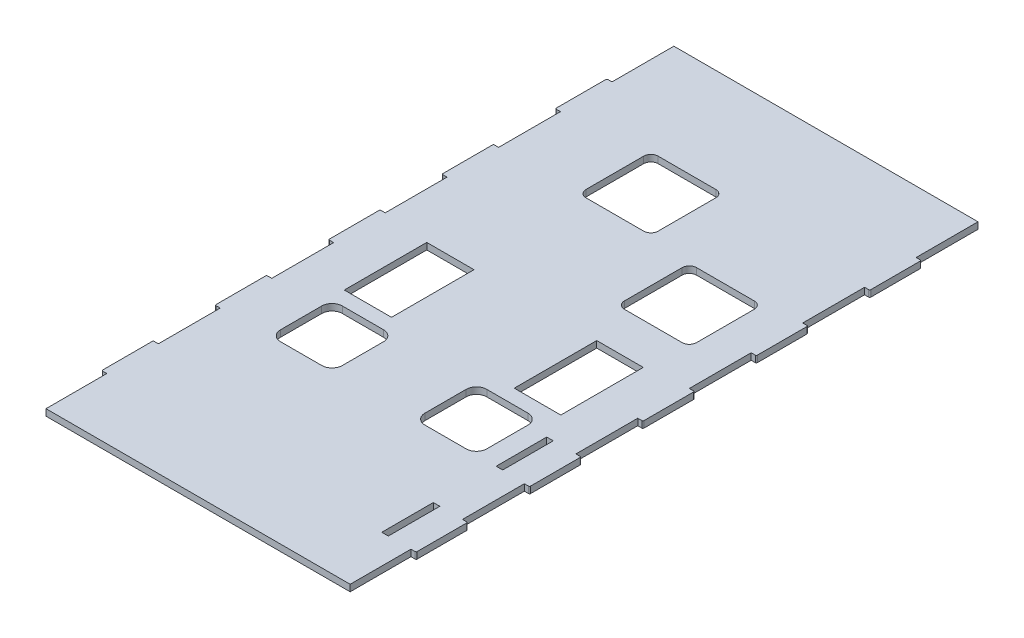
SolidWorks part; units mm, degrees
material "Oak"
ref_plane "Front Plane" through (0, 0, 0) normal (0, 0, 1) x (1, 0, 0)
ref_plane "Top Plane" through (0, 0, 0) normal (0, 1, 0) x (1, 0, 0)
ref_plane "Right Plane" through (0, 0, 0) normal (1, 0, 0) x (0, 0, -1)
sketch "Sketch1" plane through (0, 0, 0) normal (0, 1, 0) x (1, 0, 0)
  line L0 (157.0736, 348.6213) -> (157.0736, 288.6213)
  line L1 (-137.9264, 348.6213) -> (157.0736, 348.6213)
  line L3 (-137.9264, -260.3787) -> (157.0859, -260.3787)
  line L9 (157.0736, 288.6213) -> (162.0736, 288.6213)
  line L10 (162.0736, 288.6213) -> (162.0859, 238.6213)
  line L11 (162.0859, 238.6213) -> (157.0859, 238.6213)
  line L12 (157.0859, 238.6213) -> (157.0859, 178.6213)
  line L13 (157.0859, 178.6213) -> (162.0859, 178.6213)
  line L14 (162.0859, 178.6213) -> (162.0859, 128.6213)
  line L15 (162.0859, 128.6213) -> (157.0859, 128.6213)
  line L16 (157.0859, 128.6213) -> (157.0859, 68.6213)
  line L17 (157.0859, 68.6213) -> (162.0859, 68.6213)
  line L18 (162.0859, 68.6213) -> (162.0859, 18.6213)
  line L19 (162.0859, 18.6213) -> (157.0859, 18.6213)
  line L20 (157.0859, 18.6213) -> (157.0859, -41.3787)
  line L21 (157.0859, -41.3787) -> (162.0859, -41.3787)
  line L22 (162.0859, -41.3787) -> (162.0859, -91.3787)
  line L23 (162.0859, -91.3787) -> (157.0859, -91.3787)
  line L24 (157.0859, -91.3787) -> (157.0859, -151.3787)
  line L25 (157.0859, -151.3787) -> (162.0859, -151.3787)
  line L26 (162.0859, -151.3787) -> (162.0859, -201.3787)
  line L27 (162.0859, -201.3787) -> (157.0859, -201.3787)
  line L28 (157.0859, -201.3787) -> (157.0859, -260.3787)
  line L29 (-137.9264, 348.6213) -> (-137.9264, 288.6213)
  line L30 (-137.9264, 288.6213) -> (-142.9387, 288.6213)
  line L31 (-142.9387, 288.6213) -> (-142.9387, 238.6213)
  line L32 (-142.9387, 238.6213) -> (-137.9264, 238.6213)
  line L33 (-137.9264, 238.6213) -> (-137.9264, 178.6213)
  line L34 (-137.9264, 178.6213) -> (-142.9387, 178.6213)
  line L35 (-142.9387, 178.6213) -> (-142.9387, 128.6213)
  line L36 (-142.9387, 128.6213) -> (-137.9264, 128.6213)
  line L37 (-137.9264, 128.6213) -> (-137.9264, 68.6213)
  line L38 (-137.9264, 68.6213) -> (-142.9387, 68.6213)
  line L39 (-142.9387, 68.6213) -> (-142.9387, 18.6213)
  line L40 (-142.9387, 18.6213) -> (-137.9264, 18.6213)
  line L41 (-137.9264, 18.6213) -> (-137.9264, -41.3787)
  line L42 (-137.9264, -41.3787) -> (-142.9264, -41.3787)
  line L43 (-142.9264, -41.3787) -> (-142.9264, -91.3787)
  line L44 (-142.9264, -91.3787) -> (-137.9264, -91.3787)
  line L45 (-137.9264, -91.3787) -> (-137.9264, -151.3787)
  line L46 (-137.9264, -151.3787) -> (-142.9387, -151.3787)
  line L47 (-142.9387, -151.3787) -> (-142.9387, -201.3787)
  line L48 (-142.9387, -201.3787) -> (-137.9264, -201.3787)
  line L49 (-137.9264, -201.3787) -> (-137.9264, -260.3787)
  line L50 (128.7359, -259.5286) -> (128.7359, -159.5286) construction
  line L51 (128.7359, -159.5286) -> (-137.9141, -110.3787) construction
  line L52 (-137.9141, -110.3787) -> (-137.9141, -60.3787) construction
  line L53 (-137.9141, -60.3787) -> (162.0859, -60.3787) construction
  line L55 (-80.4688, -30.3787) -> (-40.4688, -30.3787)
  line L56 (-90.4688, -40.3787) -> (-90.4688, -80.3787)
  line L57 (-80.4688, -90.3787) -> (-40.4688, -90.3787)
  line L58 (-30.4688, -40.3787) -> (-30.4688, -80.3787)
  line L59 (-90.4688, -30.3787) -> (-30.4688, -90.3787) construction
  line L60 (-90.4688, -90.3787) -> (-30.4688, -30.3787) construction
  line L61 (59.5859, -30.3787) -> (99.5859, -30.3787)
  line L62 (49.5859, -40.3787) -> (49.5859, -80.3787)
  line L63 (59.5859, -90.3787) -> (99.5859, -90.3787)
  line L64 (109.5859, -40.3787) -> (109.5859, -80.3787)
  line L65 (49.5859, -30.3787) -> (109.5859, -90.3787) construction
  line L66 (49.5859, -90.3787) -> (109.5859, -30.3787) construction
  line L67 (128.7359, -201.3787) -> (135.0859, -201.3787)
  line L68 (128.7359, -201.3787) -> (128.7359, -151.3787)
  line L69 (128.7359, -151.3787) -> (135.0859, -151.3787)
  line L70 (135.0859, -201.3787) -> (135.0859, -151.3787)
  line L71 (128.7359, -90.3787) -> (135.0859, -90.3787)
  line L72 (128.7359, -90.3787) -> (128.7359, -41.3787)
  line L73 (128.7359, -41.3787) -> (135.0859, -41.3787)
  line L74 (135.0859, -90.3787) -> (135.0859, -41.3787)
  line L75 (-53.198, 248.6213) -> (2.802, 248.6213)
  line L76 (-60.198, 241.6213) -> (-60.198, 185.6213)
  line L77 (-53.198, 178.6213) -> (2.802, 178.6213)
  line L78 (9.802, 241.6213) -> (9.802, 185.6213)
  line L83 (59.0859, 173.6213) -> (115.0859, 173.6213)
  line L84 (52.0859, 166.6213) -> (52.0859, 110.6213)
  line L85 (59.0859, 103.6213) -> (115.0859, 103.6213)
  line L86 (122.0859, 166.6213) -> (122.0859, 110.6213)
  line L87 (-92.9264, 63.9367) -> (-47.1008, 63.9367)
  line L88 (-92.9264, 63.9367) -> (-92.9264, -16.0633)
  line L89 (-92.9264, -16.0633) -> (-47.1008, -16.0633)
  line L90 (-47.1008, 63.9367) -> (-47.1008, -16.0633)
  line L91 (71.9462, 63.9367) -> (117.0859, 63.9367)
  line L92 (71.9462, 63.9367) -> (71.9462, -16.0633)
  line L93 (71.9462, -16.0633) -> (117.0859, -16.0633)
  line L94 (117.0859, 63.9367) -> (117.0859, -16.0633)
  arc A0 (99.5859, -30.3787) -> (109.5859, -40.3787) centre (99.5859, -40.3787) cw
  arc A1 (109.5859, -80.3787) -> (99.5859, -90.3787) centre (99.5859, -80.3787) cw
  arc A2 (59.5859, -90.3787) -> (49.5859, -80.3787) centre (59.5859, -80.3787) cw
  arc A3 (49.5859, -40.3787) -> (59.5859, -30.3787) centre (59.5859, -40.3787) cw
  arc A4 (-90.4688, -80.3787) -> (-80.4688, -90.3787) centre (-80.4688, -80.3787) ccw
  arc A5 (-40.4688, -90.3787) -> (-30.4688, -80.3787) centre (-40.4688, -80.3787) ccw
  arc A6 (-40.4688, -30.3787) -> (-30.4688, -40.3787) centre (-40.4688, -40.3787) cw
  arc A7 (-80.4688, -30.3787) -> (-90.4688, -40.3787) centre (-80.4688, -40.3787) ccw
  arc A12 (2.802, 248.6213) -> (9.802, 241.6213) centre (2.802, 241.6213) cw
  arc A13 (9.802, 185.6213) -> (2.802, 178.6213) centre (2.802, 185.6213) cw
  arc A14 (-53.198, 178.6213) -> (-60.198, 185.6213) centre (-53.198, 185.6213) cw
  arc A15 (-60.198, 241.6213) -> (-53.198, 248.6213) centre (-53.198, 241.6213) cw
  arc A16 (115.0859, 173.6213) -> (122.0859, 166.6213) centre (115.0859, 166.6213) cw
  arc A17 (122.0859, 110.6213) -> (115.0859, 103.6213) centre (115.0859, 110.6213) cw
  arc A18 (59.0859, 103.6213) -> (52.0859, 110.6213) centre (59.0859, 110.6213) cw
  arc A19 (52.0859, 166.6213) -> (59.0859, 173.6213) centre (59.0859, 166.6213) cw
  point P46 (-90.4141, -60.3787)
  point P54 (61.387, -60.3787)
  point P97 (122.0859, 173.6213)
  point P107 (52.0859, 103.6213)
  point P110 (52.0859, 173.6213)
  point P114 (9.802, 248.6213)
  point P119 (-60.198, 178.6213)
  point P122 (-60.198, 248.6213)
  dimension "D29" = 10
  dimension "D38" = 175
  dimension "D37" = 7
  dimension "D1" = 295
  dimension "D2" = 609
  dimension "D3" = 60
  dimension "D4" = 5
  dimension "D5" = 50
  dimension "D6" = 60
  dimension "D7" = 50
  dimension "D8" = 60
  dimension "D9" = 50
  dimension "D10" = 60
  dimension "D11" = 50
  dimension "D12" = 60
  dimension "D13" = 59
  dimension "D14" = 50
  dimension "D15" = 5
  dimension "D16" = 5
  dimension "D17" = 28.35
  dimension "D18" = 100
  dimension "D19" = 150
  dimension "D20" = 50
  dimension "D21" = 47.5
  dimension "D22" = 60
  dimension "D23" = 60
  dimension "D24" = 30
  dimension "D25" = 60
  dimension "D26" = 60
  dimension "D27" = 30
  dimension "D28" = 47.5
  dimension "D30" = 6.35
  dimension "D31" = 6.35
  dimension "D32" = 70
  dimension "D33" = 70
  dimension "D34" = 70
  dimension "D35" = 70
  dimension "D36" = 100
  dimension "D39" = 80
  dimension "D40" = 80
  dimension "D41" = 40
  dimension "D42" = 35
  dimension "D43" = 45
extrude "Boss-Extrude1" add sketch "Sketch1" along normal blind 6.35
fillet "Fillet1" radius 1 20 edges at (-142.9387, 3.175, -288.6213) (-142.9387, 3.175, -238.6213) (-142.9387, 3.175, -178.6213) (-142.9387, 3.175, -128.6213) (-142.9387, 3.175, -68.6213) (-142.9387, 3.175, -18.6213) (-142.9264, 3.175, 41.3787) (-142.9264, 3.175, 91.3787) (-140.4325, 0, 151.3787) (-142.9387, 3.175, 201.3787) (162.0736, 3.175, -288.6213) (162.0859, 3.175, -238.6213) (162.0859, 3.175, -178.6213) (162.0859, 3.175, -128.6213) (162.0859, 3.175, -68.6213) (162.0859, 3.175, -18.6213) (162.0859, 3.175, 41.3787) (162.0859, 3.175, 91.3787) (162.0859, 3.175, 151.3787) (162.0859, 3.175, 201.3787)
